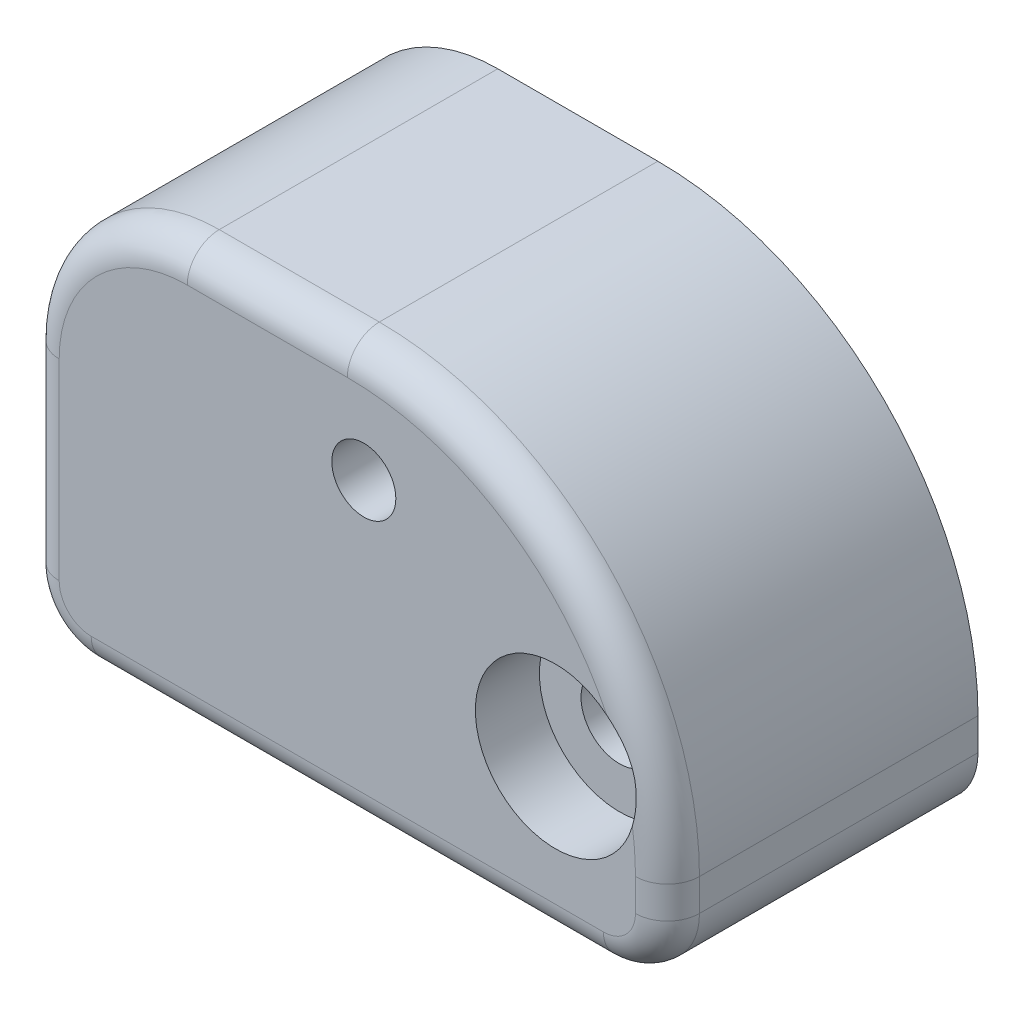
SolidWorks part; units mm, degrees
ref_plane "Front Plane" through (0, 0, 0) normal (0, 0, 1) x (1, 0, 0)
ref_plane "Top Plane" through (0, 0, 0) normal (0, 1, 0) x (1, 0, 0)
ref_plane "Right Plane" through (0, 0, 0) normal (1, 0, 0) x (0, 0, -1)
sketch "Sketch1" plane through (0, 0, 0) normal (0, 0, 1) x (1, 0, 0)
  line L0 (0, 0) -> (0, 13)
  line L1 (0, -55) -> (0, 55) construction
  line L2 (0, 13) -> (20, 13)
  line L3 (20, 13) -> (20, 0)
  line L4 (55, 0) -> (-55, 0) construction
  line L5 (20, 0) -> (0, 0)
  line L6 (20, 5) -> (0, 5) construction
  circle A1 centre (16.5, 5) radius 1.2
  dimension "D1" = 5
extrude "Boss-Extrude1" add sketch "Sketch1" along normal blind 5.8
sketch "Sketch2" plane through (0, 0, 5.8) normal (0, 0, 1) x (1, 0, 0)
  circle A0 centre (16.5, 5) radius 2.5
extrude "Cut-Extrude1" cut sketch "Sketch2" against normal blind 2
sketch "Sketch3" plane through (0, 0, 0) normal (-1, 0, 0) x (0, 0, 1)
  line L0 (5.8, 0) -> (5.8, 5) construction
  line L1 (3.19, 0) -> (-3.19, 0) construction
  line L2 (5.8, 13) -> (5.8, 0) construction
  line L3 (5.8, 5) -> (2.8, 5) construction
  circle A0 centre (2.8, 5) radius 1.5
extrude "Cut-Extrude2" cut sketch "Sketch3" against normal blind 10
sketch "Sketch4" plane through (0, 0, 5.8) normal (0, 0, 1) x (1, 0, 0)
  line L0 (20, 13) -> (20, 3) construction
  line L1 (20, 0) -> (20, 13) construction
  line L2 (20, 3) -> (10, 3) construction
fillet "Fillet1" radius 10 1 edges at (20, 13, 2.9)
fillet "Fillet2" radius 5 1 edges at (0, 13, 2.9)
fillet "Fillet3" radius 2 2 edges at (0, 0, 2.9) (20, 0, 2.9)
fillet "Fillet4" radius 1 8 edges at (17.0711, 10.0711, 5.8) (20, 2.5, 5.8) (19.4142, 0.5858, 5.8) (10, 0, 5.8) (0.5858, 0.5858, 5.8) (0, 5, 5.8) (1.4645, 11.5355, 5.8) (7.5, 13, 5.8)
sketch "Sketch5" plane through (0, 0, 0) normal (0, 0, -1) x (-1, 0, 0)
  line L8 (-20, 3) -> (-20, 2)
  line L9 (-18, 0) -> (-2, 0)
  line L10 (0, 2) -> (0, 8)
  line L11 (-5, 13) -> (-10, 13)
  line L12 (-20, 3) -> (-20, 2)
  line L13 (-18, 0) -> (-2, 0)
  line L14 (0, 2) -> (0, 8)
  line L15 (-5, 13) -> (-10, 13)
  circle A4 centre (-16.5, 5) radius 1.2
  arc A8 (-20, 2) -> (-18, 0) centre (-18, 2) ccw
  arc A9 (-2, 0) -> (0, 2) centre (-2, 2) ccw
  arc A10 (0, 8) -> (-5, 13) centre (-5, 8) ccw
  arc A11 (-10, 13) -> (-20, 3) centre (-10, 3) ccw
  arc A12 (-20, 2) -> (-18, 0) centre (-18, 2) ccw
  arc A13 (-2, 0) -> (0, 2) centre (-2, 2) ccw
  arc A14 (0, 8) -> (-5, 13) centre (-5, 8) ccw
  arc A15 (-10, 13) -> (-20, 3) centre (-10, 3) ccw
  dimension "D1" = 0
extrude "Boss-Extrude2" add sketch "Sketch5" along normal blind 3.9
sketch "Sketch6" plane through (0, 0, 5.8) normal (0, 0, 1) x (1, 0, 0)
  circle A0 centre (10.5155, 9.4816) radius 1
  point P2 (11.1817, 9.082)
  point P3 (10.6667, 9.0459)
  point P4 (10.5155, 9.4816)
extrude "Cut-Extrude3" cut sketch "Sketch6" against normal through all both and the other way through all
